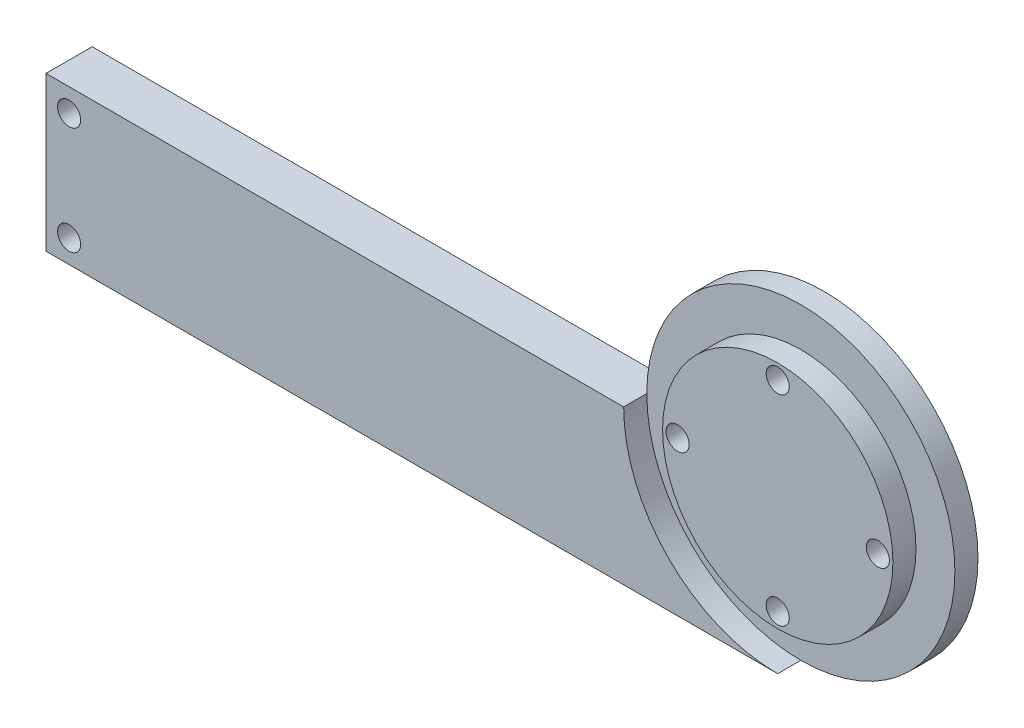
SolidWorks part; units mm, degrees
ref_plane "Plan de face" through (0, 0, 0) normal (0, 0, 1) x (1, 0, 0)
ref_plane "Plan de dessus" through (0, 0, 0) normal (0, 1, 0) x (1, 0, 0)
ref_plane "Plan de droite" through (0, 0, 0) normal (1, 0, 0) x (0, 0, -1)
sketch "Esquisse1" plane through (0, 0, 0) normal (0, 0, 1) x (1, 0, 0)
  line L1 (-45.5828, 28.0993) -> (32.9922, 28.0993)
  line L2 (-45.5828, 28.0993) -> (-45.5828, 8.0993)
  line L3 (-45.5828, 8.0993) -> (32.9922, 8.0993)
  line L4 (32.9922, 28.0993) -> (32.9922, 8.0993)
  circle A0 centre (32.9922, 28.0993) radius 20
  dimension "D3" = 40
  dimension "D1" = 0
  dimension "D2" = 20
  dimension "D4" = 0
extrude "Boss.-Extru.1" add sketch "Esquisse1" along normal blind 6 contours L4 A0 L1 | L1 A0 L4 | A0 L1 L2 L3 region at (-13.9908, 17.7215, 0) region at (35.8217, 30.9287, 0) region at (24.504, 19.611, 0)
sketch "Esquisse4" plane through (0, 0, 6) normal (0, 0, 1) x (1, 0, 0)
  circle A0 centre (32.9922, 28.0993) radius 14.95
  arc A1 (32.9922, 8.0993) -> (12.9922, 28.0993) centre (32.9922, 28.0993) ccw construction
  circle A2 centre (32.9922, 28.0993) radius 20
  dimension "D1" = 0
  dimension "D2" = 29.9
extrude "Enlèv. mat.-Extru.2" cut sketch "Esquisse4" against normal blind 3
sketch "Esquisse5" plane through (0, 0, 6) normal (0, 0, 1) x (1, 0, 0)
  line L0 (-45.5828, 28.0993) -> (12.9922, 28.0993) construction
  line L1 (-45.5828, 8.0993) -> (-62.0028, 8.0993)
  line L2 (-45.5828, 8.0993) -> (-45.5828, 28.0993)
  line L3 (-45.5828, 28.0993) -> (-62.0028, 28.0993)
  line L4 (-62.0028, 8.0993) -> (-62.0028, 28.0993)
  dimension "D1" = 0
  dimension "D2" = 16.42
  dimension "D3" = 20
extrude "Boss.-Extru.2" add sketch "Esquisse5" against normal blind 6
sketch "Esquisse6" plane through (0, 0, 6) normal (0, 0, 1) x (1, 0, 0)
  circle A0 centre (32.9922, 28.0993) radius 13 construction
  circle A1 centre (32.9922, 28.0993) radius 14.95 construction
  circle A2 centre (32.9922, 41.0993) radius 1.5
  circle A3 centre (45.9922, 28.0993) radius 1.5
  circle A4 centre (32.9922, 15.0993) radius 1.5
  circle A5 centre (19.9922, 28.0993) radius 1.5
  dimension "D1" = 0
  dimension "D2" = 26
  dimension "D3" = 3
  dimension "D4" = 3
  dimension "D5" = 3
  dimension "D6" = 3
extrude "Enlèv. mat.-Extru.3" cut sketch "Esquisse6" against normal blind 10
sketch "Esquisse8" plane through (0, 0, 0) normal (0, 0, -1) x (-1, 0, 0)
  circle A0 centre (-32.9922, 28.0993) radius 20
  arc A1 (-12.9922, 28.0993) -> (-32.9922, 8.0993) centre (-32.9922, 28.0993) ccw construction
  circle A2 centre (-32.9922, 28.0993) radius 15
  dimension "D1" = 0
sketch "Esquisse9" plane through (0, 0, 0) normal (0, 0, -1) x (-1, 0, 0)
  line L0 (59.0028, 45.4498) -> (59.0028, -4.8699) construction
  line L1 (62.0028, 28.0993) -> (62.0028, 8.0993) construction
  line L2 (62.0028, 28.0993) -> (-12.9922, 28.0993) construction
  line L3 (62.0028, 8.0993) -> (-32.9922, 8.0993) construction
  circle A0 centre (59.0028, 25.0993) radius 1.5
  circle A1 centre (59.0028, 11.0993) radius 1.5
  dimension "D2" = 3
  dimension "D3" = 3
  dimension "D4" = 3
  dimension "D5" = 3
  dimension "D1" = 3
extrude "Enlèv. mat.-Extru.4" cut sketch "Esquisse9" against normal blind 10
